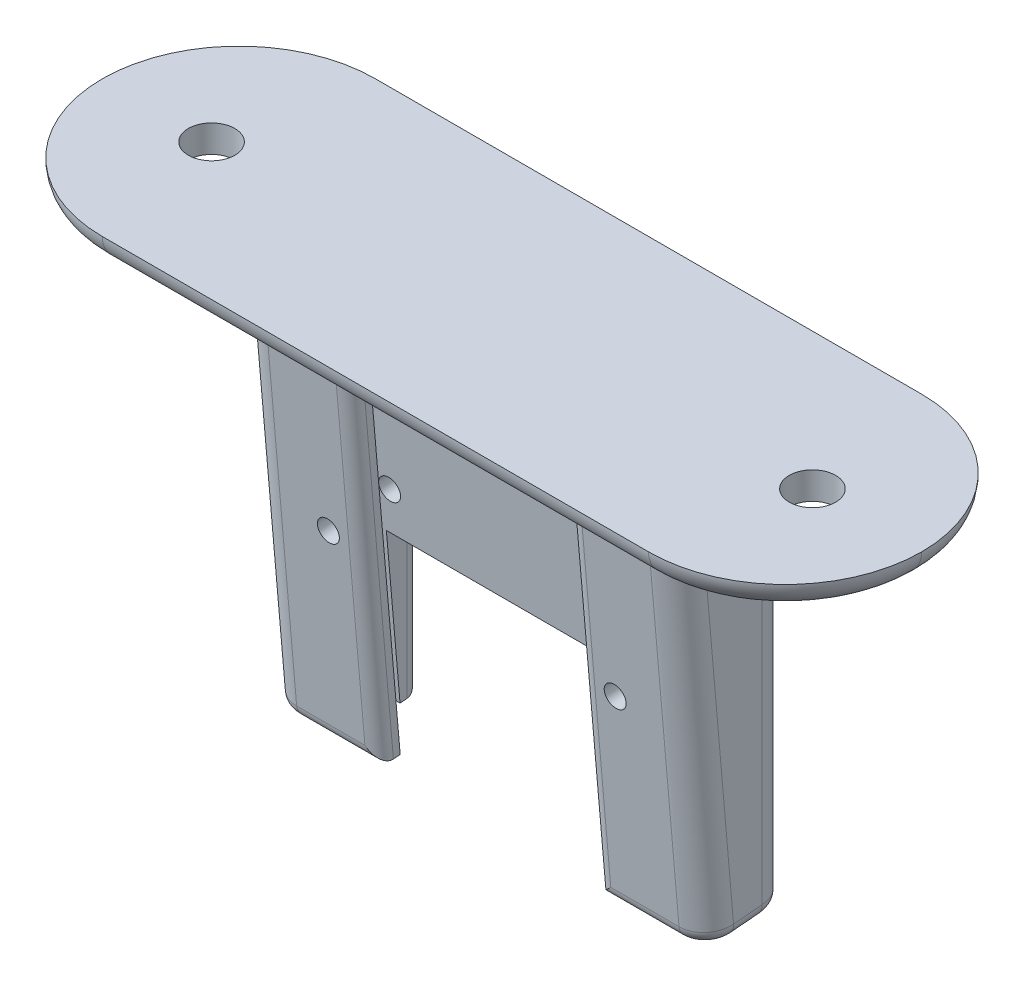
SolidWorks part; units mm, degrees
ref_plane "Plan de face" through (0, 0, 0) normal (0, 0, 1) x (1, 0, 0)
ref_plane "Plan de dessus" through (0, 0, 0) normal (0, 1, 0) x (1, 0, 0)
ref_plane "Plan de droite" through (0, 0, 0) normal (1, 0, 0) x (0, 0, -1)
sketch "Esquisse1" plane through (0, 0, 0) normal (0, 1, 0) x (1, 0, 0)
  line L0 (0, -55) -> (0, 55) construction
  line L1 (-30, 10) -> (30, 10)
  line L2 (-30, 10) -> (-30, -10)
  line L3 (-30, -10) -> (30, -10)
  line L4 (30, 10) -> (30, -10)
  line L5 (-55, 0) -> (55, 0) construction
  point P6 (0, -10)
  point P11 (30, 0)
  dimension "D1" = 60
  dimension "D2" = 20
extrude "Boss.-Extru.1" add sketch "Esquisse1" along normal blind 2
sketch "Esquisse23" plane through (0, 0, 0) normal (1, 0, 0) x (0, 0, -1)
  line L0 (-4.2959, 0) -> (4.2959, 0)
  line L1 (4.2959, 0) -> (4.2959, -29.3629)
  line L2 (4.2959, -29.3629) -> (-1.6812, -29.8858)
  line L3 (-1.6812, -29.8858) -> (-4.2959, 0)
  point P7 (0, 0)
  dimension "D1" = 85
  dimension "D2" = 6
  dimension "D3" = 30
extrude "Boss.-Extru.4" add sketch "Esquisse23" along normal mid plane 32
sketch "Esquisse24" plane through (0, -29.5129, -2.582) normal (0, -0.9962, -0.0872) x (1, 0, 0)
  line L0 (-16, 4.2796) -> (16, -1.7204) construction
  line L1 (-13, 2.7796) -> (13, 2.7796)
  line L2 (-13, 2.7796) -> (-13, -0.2204)
  line L3 (-13, -0.2204) -> (13, -0.2204)
  line L4 (13, 2.7796) -> (13, -0.2204)
  line L5 (-13, -0.2204) -> (13, 2.7796) construction
  point P9 (0, 1.2796)
  dimension "D1" = 26
  dimension "D2" = 3
extrude "Enlèv. mat.-Extru.9" cut sketch "Esquisse24" against normal blind 29
sketch "Esquisse25" plane through (0, -29.5129, -2.582) normal (0, -0.9962, -0.0872) x (1, 0, 0)
  line L0 (16, 4.2796) -> (-16, 4.2796) construction
  line L1 (-8, 4.2796) -> (8, 4.2796)
  line L2 (-8, 4.2796) -> (-8, 2.7796)
  line L3 (-8, 2.7796) -> (8, 2.7796)
  line L4 (8, 4.2796) -> (8, 2.7796)
  line L5 (13, 2.7796) -> (-13, 2.7796) construction
  line L6 (16, 4.2796) -> (-16, 4.2796) construction
  point P9 (0, 4.2796)
  dimension "D1" = 16
extrude "Enlèv. mat.-Extru.10" cut sketch "Esquisse25" against normal offset from surface (27 mm away) 2 up to face at (0, -0.7347, 1.2202)
sketch "Esquisse27" plane through (0, 0.0192, -0.2196) normal (0, -0.0872, 0.9962) x (1, 0, 0)
  line L0 (-13, -29.6256) -> (13, -29.6256) construction
  line L1 (-11, -29.6256) -> (11, -29.6256)
  line L2 (-11, -29.6256) -> (-11, -18.1256)
  line L3 (-11, -18.1256) -> (11, -18.1256)
  line L4 (11, -29.6256) -> (11, -18.1256)
  line L5 (-13, -0.6256) -> (13, -0.6256) construction
  point P9 (0, -29.6256)
  dimension "D1" = 22
  dimension "D2" = 17.5
extrude "Enlèv. mat.-Extru.12" cut sketch "Esquisse27" against normal blind 10
sketch "Esquisse28" plane through (0, -0.373, 4.2633) normal (0, -0.0872, 0.9962) x (1, 0, 0)
  line L1 (-10.5, -2.6256) -> (-16, 0.3744) construction
  line L2 (10.5, -2.6256) -> (16, 0.3744) construction
  line L3 (-13, -0.6256) -> (13, -0.6256) construction
  point P0 (-10.5, -2.6256)
  point P1 (10.5, -2.6256)
  point P2 (10.5, -15.1256)
  point P3 (-10.5, -15.1256)
  dimension "D1" = 21
  dimension "D2" = 12.5
  dimension "D3" = 2
hole_wizard "Trou pour taraudage pour trou taraudé M21" positions "Esquisse29" profile "Esquisse31" hole size "M2" standard "ISO"
sketch "Esquisse29" plane through (0, -0.373, 4.2633) normal (0, -0.0872, 0.9962) x (1, 0, 0)
  point P2 (-10.5, -2.6256)
  point P5 (-10.5, -15.1256)
  point P8 (10.5, -2.6256)
  point P23 (10.5, -15.1256)
sketch "Esquisse31" plane through (-10.5, -2.9886, 4.0345) normal (1, 0, 0) x (0, -0.9962, -0.0872)
  line L0 (0, 0) -> (0, 12.4807)
  line L1 (0, 12.4807) -> (0.8, 12)
  line L2 (0.8, 12) -> (0.8, 0)
  line L5 (0.8, 0) -> (0, 0)
  line L10 (0, 12.4807) -> (-0.8, 12) construction
  line L11 (0, -6.35) -> (0, 107.95) construction
  dimension "Diamètre du perçage" = 1.6
  dimension "Profondeur du perçage" = 12
  dimension "Angle de pointe" = 118
fillet "Congé7" radius 10 4 edges at (-30, 1, -10) (30, 1, -10) (30, 1, 10) (-30, 1, 10)
fillet "Congé5" radius 2 10 edges at (-16, -14.6815, -4.2959) (16, -14.6815, -4.2959) (16, -14.9429, 2.9886) (-16, -14.9429, 2.9886) (0, 0, -10) (0, 0, 10) (-27.0711, 0, 7.0711) (-27.0711, 0, -7.0711) (27.0711, 0, -7.0711) (27.0711, 0, 7.0711)
fillet "Congé6" radius 1 24 edges at (12.5, -29.3629, -4.2959) (15.4142, -29.4142, -3.7101) (16, -29.6247, -1.3035) (15.4142, -29.8348, 1.0977) (-12.5, -29.3629, -4.2959) (-15.4142, -29.4142, -3.7101) (-16, -29.6247, -1.3035) (-15.4142, -29.8348, 1.0977) (15.4142, 0, 3.7079) (16, 0, -0.0038) (15.4142, 0, -3.7101) (0, 0, -4.2959) (-15.4142, 0, -3.7101) (-16, 0, -0.0038) (-15.4142, 0, 3.7079) (11, -29.8858, 1.6812) (-11, -29.8858, 1.6812) (0, -2.9886, 4.0345) (-11, -23.5909, -4.2959) (11, -23.5909, -4.2959) (0, -17.819, -4.2959) (8, -16.4372, 2.8579) (-8, -16.4372, 2.8579) (0, 0, 4.2959)
hole_wizard "Dégagement M31" positions "Esquisse32" profile "Esquisse33" hole size "M3" standard "ISO"
sketch "Esquisse32" plane through (0, 0, 0) normal (0, -1, 0) x (-1, 0, 0)
  line L0 (22, 0) -> (-22, 0) construction
  point P0 (22, 0)
  point P2 (-22, 0)
  point P74 (23.0965, 0)
  point P75 (0, 0)
  point P76 (0, 0)
  point P77 (-19.445, 0)
  dimension "D1" = 44
sketch "Esquisse33" plane through (-22, 0, 0) normal (1, 0, 0) x (0, 0, -1)
  line L0 (0, 0) -> (0, 6.0215)
  line L1 (0, 6.0215) -> (1.7, 5)
  line L2 (1.7, 5) -> (1.7, 0)
  line L5 (1.7, 0) -> (0, 0)
  line L10 (0, 6.0215) -> (-1.7, 5) construction
  line L11 (0, -6.35) -> (0, 107.95) construction
  dimension "Diamètre du perçage" = 3.4
  dimension "Profondeur du perçage" = 5
  dimension "Angle de pointe" = 118
